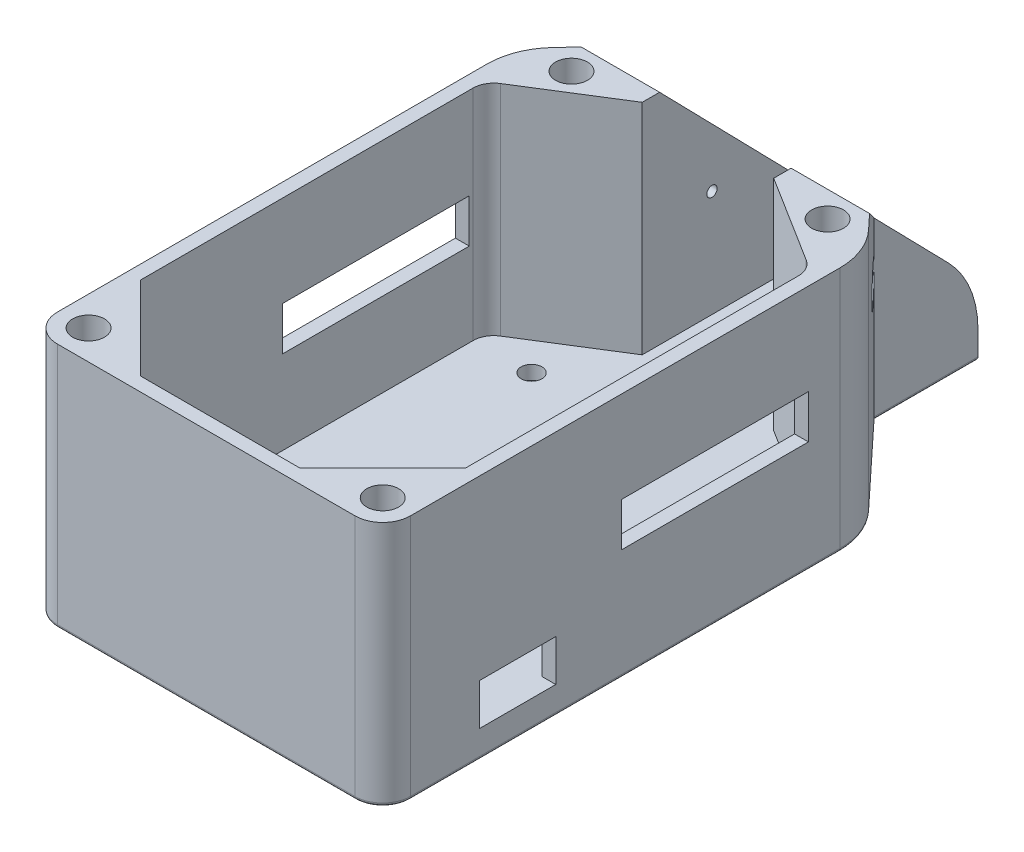
SolidWorks part; units mm, degrees
ref_plane "Front Plane" through (0, 0, 0) normal (0, 0, 1) x (1, 0, 0)
ref_plane "Top Plane" through (0, 0, 0) normal (0, 1, 0) x (1, 0, 0)
ref_plane "Right Plane" through (0, 0, 0) normal (1, 0, 0) x (0, 0, -1)
sketch "Sketch1" plane through (0, -17.9455, 0) normal (0, -1, 0) x (1, 0, 0)
  line L0 (-7.9447, 39.1511) -> (-7.9447, 84.1511) construction
  line L1 (40.0553, 4.1511) -> (-10.9447, 4.1511)
  line L2 (40.0553, 4.1511) -> (40.0553, 104.1511)
  line L3 (40.0553, 104.1511) -> (-10.9447, 104.1511)
  line L4 (-10.9447, 4.1511) -> (-10.9447, 104.1511)
  line L5 (37.0553, 84.1511) -> (37.0553, 39.1511) construction
  line L6 (37.0553, 39.1511) -> (-7.9447, 39.1511) construction
  line L7 (-7.9447, 84.1511) -> (37.0553, 84.1511) construction
  line L8 (40.0553, 34.1511) -> (26.0553, 19.1511)
  line L9 (26.0553, 19.1511) -> (26.0553, 4.1511)
  line L10 (3.0553, 4.1511) -> (3.0553, 19.1511)
  line L11 (3.0553, 19.1511) -> (-10.9447, 34.1511)
  line L12 (5.0553, 27.2658) -> (5.0553, 33.1063) construction
  line L13 (24.0553, 27.2658) -> (24.0553, 33.1063) construction
  circle M7 centre (-0.6947, 41.9011) radius 1.25
  arc M8 (0.5553, 39.736) -> (1.8053, 41.9011) centre (-0.6947, 41.9011) ccw
  arc M9 (1.8053, 41.9011) -> (0.5553, 44.0662) centre (-0.6947, 41.9011) ccw
  arc M10 (0.5553, 44.0662) -> (-1.9447, 44.0662) centre (-0.6947, 41.9011) ccw
  arc M11 (-1.9447, 44.0662) -> (-3.1947, 41.9011) centre (-0.6947, 41.9011) ccw
  arc M12 (-3.1947, 41.9011) -> (-1.9447, 39.736) centre (-0.6947, 41.9011) ccw
  arc M13 (-1.9447, 39.736) -> (0.5553, 39.736) centre (-0.6947, 41.9011) ccw
  dimension "D1" = 3
  dimension "D2" = 3
  dimension "D3" = 35
  dimension "D4" = 20
  dimension "D5" = 15
  dimension "D6" = 15
  dimension "D7" = 15
  dimension "D8" = 15
  dimension "D9" = 2
  dimension "D10" = 2
extrude "Boss-Extrude1" add sketch "Sketch1" along normal blind 4 contours L11 L10 L1 L9 L8 L2 L3 L4 M8 M13 M12 M11 M10 M9 | M13 M8 M9 M10 M11 M12 M7 | M7 region at (14.6226, -17.9455, 59.6317) region at (-0.6947, -17.9455, 41.9011) region at (-0.6947, -17.9455, 39.4718)
sketch "Sketch2" plane through (0, -17.9455, 0) normal (0, 1, 0) x (1, 0, 0)
  line L8 (5.0553, -19.9394) -> (5.0553, -31.6642)
  line L9 (5.0553, -31.6642) -> (-8.9447, -46.6642) construction
  line L10 (24.0553, -19.9394) -> (24.0553, -31.6642)
  line L11 (24.0553, -31.6642) -> (38.0553, -46.6642) construction
  line L12 (5.0553, -31.6642) -> (-8.9447, -40.4394)
  line L13 (24.0553, -31.6642) -> (38.0553, -40.4394)
  line L16 (5.0553, -19.9394) -> (-8.9447, -34.9394)
  line L17 (-8.9447, -34.9394) -> (-8.9447, -102.1511)
  line L18 (-8.9447, -102.1511) -> (38.0553, -102.1511)
  line L19 (38.0553, -102.1511) -> (38.0553, -34.9394)
  line L20 (38.0553, -34.9394) -> (24.0553, -19.9394)
  line L21 (24.0553, -19.9394) -> (24.0553, -6.1511)
  line L22 (24.0553, -6.1511) -> (5.0553, -6.1511)
  line L23 (5.0553, -6.1511) -> (5.0553, -19.9394)
  line L24 (5.0553, -19.9394) -> (-8.9447, -34.9394)
  line L25 (-8.9447, -34.9394) -> (-8.9447, -102.1511)
  line L26 (-8.9447, -102.1511) -> (38.0553, -102.1511)
  line L27 (38.0553, -102.1511) -> (38.0553, -34.9394)
  line L28 (38.0553, -34.9394) -> (24.0553, -19.9394)
  line L29 (24.0553, -19.9394) -> (24.0553, -6.1511)
  line L30 (24.0553, -6.1511) -> (5.0553, -6.1511)
  line L31 (5.0553, -6.1511) -> (5.0553, -19.9394)
  line M9 (3.0553, -19.1511) -> (-10.9447, -34.1511)
  line M10 (-10.9447, -34.1511) -> (-10.9447, -104.1511)
  line M11 (-10.9447, -104.1511) -> (40.0553, -104.1511)
  line M12 (40.0553, -104.1511) -> (40.0553, -34.1511)
  line M13 (40.0553, -34.1511) -> (26.0553, -19.1511)
  line M14 (26.0553, -19.1511) -> (26.0553, -4.1511)
  line M15 (26.0553, -4.1511) -> (3.0553, -4.1511)
  line M16 (3.0553, -4.1511) -> (3.0553, -19.1511)
  dimension "D2" = 8
  dimension "D3" = 8
  dimension "D4" = 5.5
  dimension "D5" = 5.5
  dimension "D1" = 2
extrude "Boss-Extrude2" add sketch "Sketch2" along normal up to surface (31.6 mm away) contours L31 L30 L29 L28 L27 L26 L25 L24 M16 M9 M10 M11 M12 M13 M14 M15 | L24 L25 L9 L8 | L27 L28 L10 L11 region at (-1.1015, -17.9455, 31.0296) region at (30.2121, -17.9455, 31.0296) region at (4.1779, -17.9455, 11.6511)
sketch "Sketch3" plane through (-10.9447, 0, 0) normal (-1, 0, 0) x (0, 0, 1)
  line L0 (29.1511, 13.6545) -> (4.1511, -11.9455)
  line L1 (4.1511, -21.9455) -> (4.1511, 13.6545) construction
  line L3 (34.1511, 13.6545) -> (19.1511, 13.6545) construction
  line L4 (29.1511, 13.6545) -> (4.1511, 13.6545)
  line L5 (19.1511, 13.6545) -> (4.1511, 13.6545) construction
  line L6 (4.1511, -11.9455) -> (4.1511, 13.6545)
  line L7 (4.1511, -21.9455) -> (19.1511, -21.9455) construction
  dimension "D1" = 5
  dimension "D2" = 10
extrude "Cut-Extrude1" cut sketch "Sketch3" against normal through all
fillet "Fillet1" radius 15 1 edges at (14.5553, -11.9455, 4.1511)
fillet "Fillet2" radius 3 2 edges at (5.0553, -14.2585, 6.1511) (24.0553, -14.2585, 6.1511)
fillet "Fillet3" radius 3 2 edges at (-8.9447, -2.1455, 40.4394) (38.0553, -2.1455, 40.4394)
sketch "Sketch4" plane through (0, -21.9455, 0) normal (0, -1, 0) x (1, 0, 0)
  circle A0 centre (29.8053, 72.4011) radius 1.25 construction
  circle A1 centre (29.8053, 41.9011) radius 1.25 construction
  circle A2 centre (-0.6947, 41.9011) radius 1.25 construction
  circle A3 centre (-0.6947, 72.4011) radius 1.25 construction
  circle A4 centre (29.8053, 72.4011) radius 1.25 construction
  circle A5 centre (29.8053, 41.9011) radius 1.25 construction
  circle A6 centre (-0.6947, 41.9011) radius 1.25 construction
  circle A7 centre (-0.6947, 72.4011) radius 1.25 construction
  circle A8 centre (-0.6947, 41.9011) radius 3.25
  circle A9 centre (-0.6947, 72.4011) radius 3.25
  circle A10 centre (29.8053, 72.4011) radius 3.25
  circle A11 centre (29.8053, 41.9011) radius 3.25
  dimension "D1" = 6.5
  dimension "D2" = 6.5
  dimension "D3" = 6.5
  dimension "D4" = 6.5
extrude "Cut-Extrude2" cut sketch "Sketch4" against normal blind 2
sketch "Sketch5" plane through (0, -19.9455, 0) normal (0, -1, 0) x (1, 0, 0)
  circle A0 centre (-0.6947, 41.9011) radius 1.5
  circle A1 centre (-0.6947, 72.4011) radius 1.5
  circle A2 centre (29.8053, 72.4011) radius 1.5
  circle A3 centre (29.8053, 41.9011) radius 1.5
  dimension "D1" = 3
  dimension "D2" = 3
  dimension "D3" = 3
  dimension "D4" = 3
extrude "Cut-Extrude3" cut sketch "Sketch5" against normal through all
chamfer "Chamfer1" distance 12 angle 45 2 edges at (-8.9447, -2.1455, 102.1511) (38.0553, -2.1455, 102.1511)
sketch "Sketch6" plane through (0, 13.6545, 0) normal (0, 1, 0) x (1, 0, 0)
  line L1 (40.0553, -104.1511) -> (-10.9447, -104.1511) construction
  line L2 (40.0553, -34.1511) -> (40.0553, -104.1511) construction
  line L3 (-10.9447, -104.1511) -> (-10.9447, -34.1511) construction
  circle A0 centre (33.0553, -32.8815) radius 2.3
  circle A1 centre (-3.9447, -32.8815) radius 2.3
  circle A2 centre (35.8053, -99.9011) radius 2.3
  circle A3 centre (-6.6947, -99.9011) radius 2.3
  dimension "D1" = 4.6
  dimension "D4" = 4.6
  dimension "D7" = 4.6
  dimension "D8" = 4.6
  dimension "D2" = 7
  dimension "D3" = 4.4
  dimension "D5" = 7
  dimension "D6" = 4.4
  dimension "D9" = 4.25
  dimension "D10" = 4.25
  dimension "D11" = 4.25
  dimension "D12" = 4.25
extrude "Cut-Extrude4" cut sketch "Sketch6" against normal blind 7
fillet "Fillet4" radius 10 2 edges at (40.0553, -4.1455, 34.1511) (-10.9447, -4.1455, 34.1511)
fillet "Fillet5" radius 4 2 edges at (40.0553, -4.1455, 104.1511) (-10.9447, -4.1455, 104.1511)
sketch "Sketch8" plane through (3.0553, 0, 0) normal (-1, 0, 0) x (0, 0, 1)
  circle A1 centre (21.5861, -2.526) radius 0.75
  circle A2 centre (21.5861, -2.526) radius 0.75
  dimension "D1" = 0
extrude "Cut-Extrude5" cut sketch "Sketch8" against normal through all and the other way through all
sketch "Sketch9" plane through (3.0553, 0, 0) normal (-1, 0, 0) x (0, 0, 1)
  circle A0 centre (21.5861, -2.526) radius 0.75 construction
  circle A1 centre (21.5861, -2.526) radius 0.75 construction
  circle A2 centre (21.5861, -2.526) radius 2.5
  dimension "D1" = 5
extrude "Cut-Extrude6" cut sketch "Sketch9" along normal through all
extrude "Cut-Extrude7" cut sketch "Sketch9<2>" against normal through all from surface starting at face at (26.0553, -13.1376, 10.7995)
sketch "Sketch9<2>" plane through (3.0553, 0, 0) normal (-1, 0, 0) x (0, 0, 1) same geometry as "Sketch9"
sketch "Sketch10" plane through (-10.9447, 0, 0) normal (-1, 0, 0) x (0, 0, 1)
  line L1 (42.6511, -5.8455) -> (69.6511, -5.8455)
  line L2 (42.6511, -5.8455) -> (42.6511, 0.4545)
  line L3 (42.6511, 0.4545) -> (69.6511, 0.4545)
  line L4 (69.6511, -5.8455) -> (69.6511, 0.4545)
  line L5 (66.2511, -1.0455) -> (67.1511, -1.0455) construction
  line L6 (67.6511, -4.3455) -> (69.6511, -4.3455) construction
  line L7 (45.1511, -4.3455) -> (45.1511, -1.5455) construction
  line L8 (67.1511, -4.3455) -> (67.1511, -1.5455) construction
  dimension "D1" = 1.5
  dimension "D2" = 1.5
  dimension "D3" = 2.5
  dimension "D4" = 2.5
extrude "Cut-Extrude8" cut sketch "Sketch10" against normal through all
fillet "Fillet6" radius 0.5 16 edges at (39.3587, -21.9455, 34.4257) (31.7106, -21.9455, 25.2103) (26.0553, -21.9455, 11.6511) (14.5553, -21.9455, 4.1511) (3.0553, -21.9455, 11.6511) (-2.6, -21.9455, 25.2103) (-10.2481, -21.9455, 34.4257) (-10.9447, -21.9455, 69.1219) (-9.7731, -21.9455, 102.9795) (14.5553, -21.9455, 104.1511) (38.8837, -21.9455, 102.9795) (40.0553, -21.9455, 69.1219) (-0.6947, -21.9455, 38.6511) (-0.6947, -21.9455, 69.1511) (29.8053, -21.9455, 69.1511) (29.8053, -21.9455, 38.6511)
sketch "Sketch11" plane through (38.0553, 0, 0) normal (-1, 0, 0) x (0, 0, 1)
  line L0 (90.1511, -17.9455) -> (42.0996, -17.9455) construction
  line L1 (90.1511, -17.9455) -> (79.1511, -17.9455)
  line L2 (90.1511, -17.9455) -> (90.1511, -11.9455)
  line L3 (90.1511, -11.9455) -> (79.1511, -11.9455)
  line L4 (79.1511, -17.9455) -> (79.1511, -11.9455)
  dimension "D1" = 6
  dimension "D2" = 11
extrude "Cut-Extrude9" cut sketch "Sketch11" against normal through all
